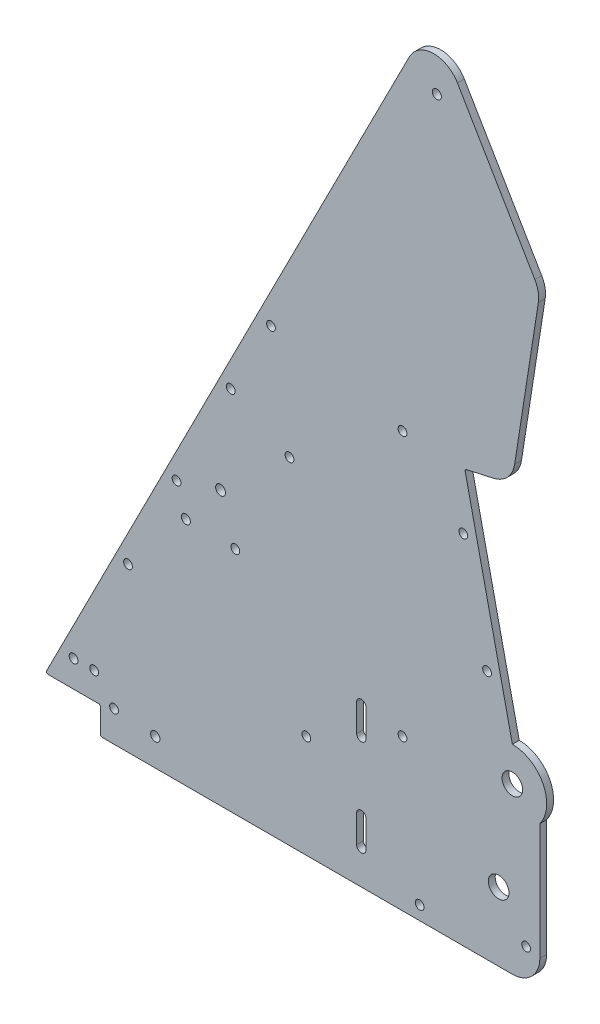
SolidWorks part; units mm, degrees
other "Markup1"
sketch "Sketch5"
ref_plane "Front Plane" through (0, 0, 0) normal (0, 0, 1) x (1, 0, 0)
ref_plane "Top Plane" through (0, 0, 0) normal (0, 1, 0) x (1, 0, 0)
ref_plane "Right Plane" through (0, 0, 0) normal (1, 0, 0) x (0, 0, -1)
sketch "Sketch1" plane through (0, 0, 0) normal (0, 0, 1) x (1, 0, 0)
  line L1 (228.6, -12.7) -> (228.6, 53.975)
  line L2 (178.7547, 351.4131) -> (0, 0)
  line L3 (228.6, 266.7) -> (178.7547, 351.4131)
  line L5 (0, 0) -> (25.4, 0)
  line L6 (25.4, 0) -> (25.4, -12.7)
  line L7 (25.4, -12.7) -> (228.6, -12.7)
  line L9 (215.9, 79.375) -> (193.9097, 178.5667)
  line L10 (193.9097, 178.5667) -> (215.6079, 183.377)
  line L11 (215.6079, 183.377) -> (228.6, 266.7)
  arc A0 (228.6, 53.975) -> (215.9, 79.375) centre (215.9, 63.5) ccw
  dimension "D7" = 12.7
  dimension "D8" = 76.2
  dimension "D10" = 31.75
  dimension "D2" = 279.4
  dimension "D3" = 25.4
  dimension "D4" = 215.9
  dimension "D5" = 394.2644
  dimension "D6" = 203.2
  dimension "D9" = 63.039
  dimension "D11" = 101.6
  dimension "D12" = 12.5
  dimension "D13" = 22.225
extrude "Boss-Extrude1" add sketch "Sketch1" along normal blind 3.175
sketch "Sketch2" plane through (0, 0, 3.175) normal (0, 0, 1) x (1, 0, 0)
  line L0 (178.7547, 351.4131) -> (0, 0) construction
  line L1 (25.4, -12.7) -> (228.6, -12.7) construction
  line L2 (215.9, 79.375) -> (193.9097, 178.5667) construction
  line L3 (193.9097, 178.5667) -> (215.6079, 183.377) construction
  line L4 (215.9, 79.375) -> (193.9097, 178.5667) construction
  line L10 (228.6, -12.7) -> (228.6, 53.975) construction
  circle A0 centre (64.9432, 94.0578) radius 2.0955
  circle A1 centre (180.975, 322.1643) radius 2.0955
  circle A2 centre (81.0071, 113.733) radius 2.286
  circle A3 centre (193.2078, 152.3944) radius 2.032
  circle A4 centre (215.9, 63.5) radius 4.7625
  circle A7 centre (173.0375, -6.35) radius 2.032
  circle A8 centre (204.203, 102.7985) radius 2.032
  circle A26 centre (209.55, 19.05) radius 4.7625
  circle A28 centre (60.6578, 107.342) radius 2.032
  arc A30 (228.6, 53.975) -> (215.9, 79.375) centre (215.9, 63.5) ccw construction
  circle A31 centre (165.1, 179.3875) radius 2.032
  circle A32 centre (87.825, 93.5227) radius 2.032
  circle A33 centre (112.8724, 142.7633) radius 2.032
  circle A34 centre (85.7052, 156.5826) radius 2.032
  dimension "D3" = 4.191
  dimension "D5" = 4.191
  dimension "D9" = 4.572
  dimension "D20" = 9.525
  dimension "D23" = 9.525
  dimension "D18" = 4.064
  dimension "D26" = 4.064
  dimension "D14" = 4.064
  dimension "D10" = 4.064
  dimension "D2" = 15.24
  dimension "D6" = 15.24
  dimension "D7" = 25.4
  dimension "D8" = 20.6375
  dimension "D21" = 44.45
  dimension "D22" = 6.35
  dimension "D19" = 160.3375
  dimension "D24" = 44.45
  dimension "D25" = 6.35
  dimension "D27" = 25.4
  dimension "D28" = 50.8
  dimension "D29" = 6.35
  dimension "D17" = 6.35
  dimension "D33" = 55.5625
  dimension "D15" = 114.3
  dimension "D4" = 180.975
extrude "Cut-Extrude1" cut sketch "Sketch2" against normal through all
sketch "Sketch7" plane through (0, 0, 3.175) normal (0, 0, 1) x (1, 0, 0)
  line L0 (146.05, 3.175) -> (146.05, 15.875) construction
  line L1 (143.891, 3.175) -> (143.891, 15.875)
  line L2 (148.209, 3.175) -> (148.209, 15.875)
  line L3 (146.05, 47.625) -> (146.05, 60.325) construction
  line L4 (143.891, 47.625) -> (143.891, 60.325)
  line L5 (148.209, 47.625) -> (148.209, 60.325)
  line L6 (25.4, -12.7) -> (228.6, -12.7) construction
  line L12 (228.6, -12.7) -> (228.6, 53.975) construction
  line L13 (25.4, -12.7) -> (228.6, -12.7) construction
  arc A0 (143.891, 3.175) -> (148.209, 3.175) centre (146.05, 3.175) ccw
  arc A1 (148.209, 15.875) -> (143.891, 15.875) centre (146.05, 15.875) ccw
  arc A2 (143.891, 47.625) -> (148.209, 47.625) centre (146.05, 47.625) ccw
  arc A3 (148.209, 60.325) -> (143.891, 60.325) centre (146.05, 60.325) ccw
  circle A8 centre (50.8, 0) radius 2.159
  point P2 (146.05, 9.525)
  point P9 (146.05, 53.975)
  dimension "D1" = 4.318
  dimension "D5" = 4.318
  dimension "D2" = 12.7
  dimension "D3" = 12.7
  dimension "D4" = 44.45
  dimension "D6" = 95.25
  dimension "D7" = 82.55
  dimension "D8" = 15.875
  dimension "D9" = 12.7
extrude "Cut-Extrude2" cut sketch "Sketch7" against normal through all
sketch "Sketch10" plane through (0, 0, 3.175) normal (0, 0, 1) x (1, 0, 0)
  circle A0 centre (120.65, 34.925) radius 2.032
  circle A1 centre (165.1, 57.15) radius 2.032
  circle A2 centre (13.0465, 12.3347) radius 2.032
  circle A3 centre (22.5715, 12.3347) radius 2.032
  circle A4 centre (38.2114, 62.6398) radius 2.032
  dimension "D1" = 4.064
  dimension "D3" = 34.925
  dimension "D2" = 120.65
  dimension "D4" = 63.5
  dimension "D5" = 69.85
extrude "Cut-Extrude3" cut sketch "Sketch10" against normal up to next
fillet "Fillet1" radius 12.7 4 edges at (228.6, -12.7, 1.5875) (178.7547, 351.4131, 1.5875) (215.6079, 183.377, 1.5875) (228.6, 266.7, 1.5875)
fillet "Fillet2" radius 0.7937 4 edges at (25.4, -12.7, 1.5875) (25.4, 0, 1.5875) (193.9097, 178.5667, 1.5875) (0, 0, 1.5875)
sketch "Sketch12" plane through (0, 0, 3.175) normal (0, 0, 1) x (1, 0, 0)
  circle A0 centre (31.75, 1.5875) radius 2.032
  circle A1 centre (173.0375, -6.35) radius 2.032
  circle A2 centre (222.25, 1.5875) radius 2.032
  dimension "D1" = 4.064
extrude "Cut-Extrude5" cut sketch "Sketch12" against normal through all
sketch "Sketch13" plane through (0, 0, 3.175) normal (0, 0, 1) x (1, 0, 0)
  line L0 (168.2448, 330.7518) -> (0.5868, 1.1536) construction
  circle A0 centre (104.3218, 191.08) radius 2.032
  dimension "D2" = 4.064
  dimension "D1" = 6.35
extrude "Cut-Extrude6" cut sketch "Sketch13" against normal through all
equation "\"D6@Sketch2\"=\"D2@Sketch2\""
